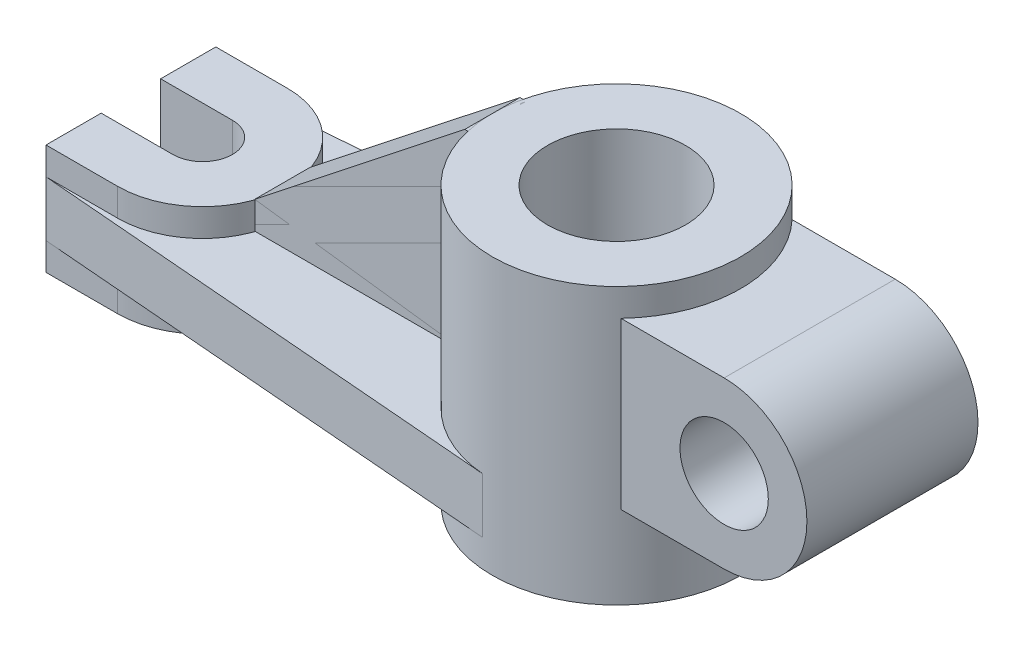
SolidWorks part; units mm, degrees
ref_plane "Front Plane" through (0, 0, 0) normal (0, 0, 1) x (1, 0, 0)
ref_plane "Top Plane" through (0, 0, 0) normal (0, 1, 0) x (1, 0, 0)
ref_plane "Right Plane" through (0, 0, 0) normal (1, 0, 0) x (0, 0, -1)
sketch "Sketch1" plane through (0, 0, 0) normal (0, 1, 0) x (1, 0, 0)
  line L0 (0, 0) -> (-75, 0)
  line L1 (-75, 15.3874) -> (-88, 15.3874)
  line L2 (-88, 15.3874) -> (-88, 5.3874)
  line L3 (-88, 5.3874) -> (-75, 5.3874)
  line L4 (-75, -5.3874) -> (-88, -5.3874)
  line L5 (-88, -5.3874) -> (-88, -15.3874)
  line L6 (-88, -15.3874) -> (-75, -15.3874)
  line L7 (-88, -15.3874) -> (-1.8316, -22.4253)
  line L8 (-88, 15.3874) -> (-1.8316, 22.4253)
  line L9 (0, 0) -> (35, 0) construction
  line L10 (35, -15.5) -> (35, 15.5)
  line L11 (35, 15.5) -> (16.3095, 15.5)
  line L12 (35, -15.5) -> (16.3095, -15.5)
  circle A0 centre (0, 0) radius 12.5
  circle A1 centre (0, 0) radius 22.5
  arc A2 (-75, 5.3874) -> (-75, -5.3874) centre (-75, 0) cw
  arc A3 (-75, 15.3874) -> (-75, -15.3874) centre (-75, 0) cw
  point P19 (35, 0)
  dimension "D1" = 45
  dimension "D2" = 25
  dimension "D3" = 75
  dimension "D4" = 13
  dimension "D5" = 10
  dimension "D6" = 35
  dimension "D7" = 31
extrude "Boss-Extrude1" add sketch "Sketch1" along normal blind 50 contours L9 A0 L0 A1 | A0 L9 A1 L0 region at (0, 0, 13.0031) region at (-17.5, 0, -0.5031)
extrude "Boss-Extrude2" add sketch "Sketch1<4>" along normal blind 20 separate body contours A3 L1 L2 L3 A2 L0 | A3 L0 A2 L4 L5 L6 region at (-73.9176, 0, 8.5708) region at (-73.9176, 0, -8.5708)
sketch "Sketch1<4>" plane through (0, 0, 0) normal (0, 1, 0) x (1, 0, 0) same geometry as "Sketch1"
extrude "Boss-Extrude4" add sketch "Sketch1<6>" along normal blind 10 from offset 5 contours L0 A3 L6 L7 A1 | L1 A3 L0 A1 L8 region at (-40.6277, 0, 10.7033) region at (-40.6277, 0, -10.7033)
sketch "Sketch1<6>" plane through (0, 0, 0) normal (0, 1, 0) x (1, 0, 0) same geometry as "Sketch1"
extrude "Boss-Extrude5" add sketch "Sketch1<7>" along normal blind 30 from offset 15 contours L9 A1 L12 L10 | A1 L9 L10 L11 region at (27.6706, 0, -8.2847) region at (27.6706, 0, 8.2847)
sketch "Sketch1<7>" plane through (0, 0, 0) normal (0, 1, 0) x (1, 0, 0) same geometry as "Sketch1"
sketch "Sketch9" plane through (0, 0, 0) normal (0, 0, 1) x (1, 0, 0)
  line L0 (-21.3685, 50) -> (-22.5, 50)
  line L1 (22.5, 50) -> (-22.5, 50) construction
  line L2 (-22.5, 50) -> (-60.5634, 20)
  line L3 (-59.6126, 20) -> (-75, 20) construction
  line L4 (-60.5634, 20) -> (-60.5634, 15)
  line L5 (-88, 15) -> (-1.8316, 15) construction
  line L6 (-60.5634, 15) -> (-21.3685, 15)
  line L7 (-21.3685, 15) -> (-21.3685, 50)
extrude "Boss-Extrude9" add sketch "Sketch9" along normal mid plane 10 separate body
sketch "Sketch12" plane through (0, 0, 15.5) normal (0, 0, 1) x (1, 0, 0)
  line L0 (35, 45) -> (35, 15) construction
  line L1 (35, 45) -> (35, 15)
  arc A0 (35, 45) -> (35, 15) centre (35, 30) cw
extrude "Boss-Extrude10" add sketch "Sketch12" against normal blind 31
sketch "Sketch13" plane through (0, 0, 15.5) normal (0, 0, 1) x (1, 0, 0)
  circle A0 centre (35, 30) radius 8
  dimension "D1" = 16
extrude "Cut-Extrude1" cut sketch "Sketch13" against normal through all both and the other way through all
extrude "Boss-Extrude11" add sketch "Sketch9<2>" along normal mid plane 10 separate body
sketch "Sketch9<2>" plane through (0, 0, 0) normal (0, 0, 1) x (1, 0, 0) same geometry as "Sketch9"
sketch "Sketch17" plane through (0, 0, 0) normal (0, -1, 0) x (1, 0, 0)
  line L0 (12.0653, 3.268) -> (50, 3.268)
  line L1 (50, -15.5) -> (50, 15.5) construction
  line L2 (50, 3.268) -> (50, -2.6317)
  line L3 (50, -2.6317) -> (12.2198, -2.6317)
  circle A0 centre (0, 0) radius 12.5 construction
